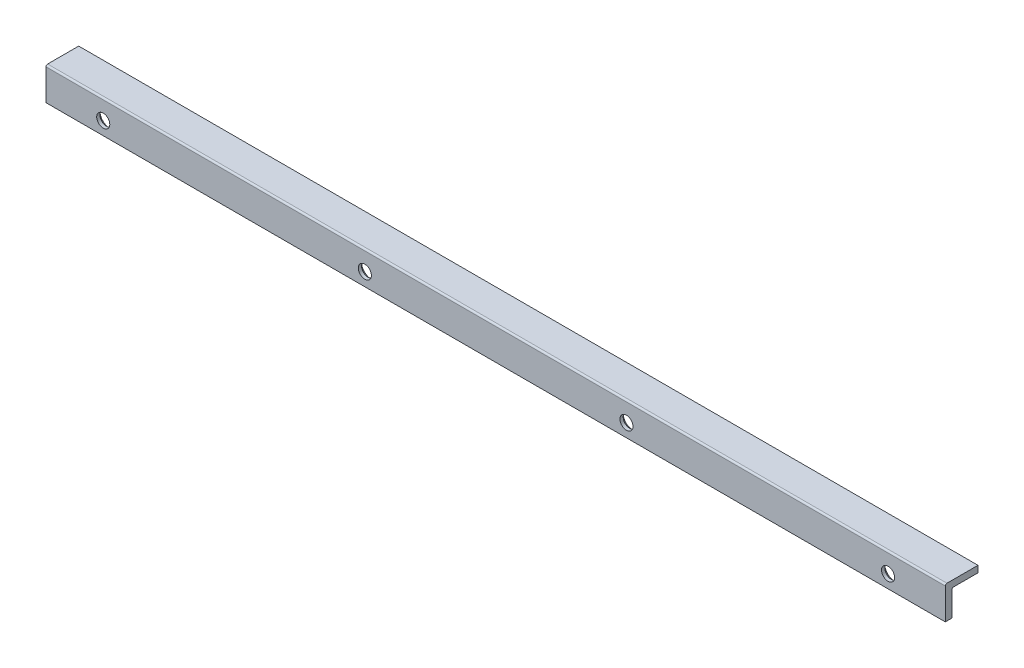
SolidWorks part; units mm, degrees
material "1060 Alloy"
ref_plane "Front Plane" through (0, 0, 0) normal (0, 0, 1) x (1, 0, 0)
ref_plane "Top Plane" through (0, 0, 0) normal (0, 1, 0) x (1, 0, 0)
ref_plane "Right Plane" through (0, 0, 0) normal (1, 0, 0) x (0, 0, -1)
sketch "Sketch1" plane through (0, 0, 0) normal (1, 0, 0) x (0, 0, -1)
  line L0 (0, -10) -> (0, -0.5)
  line L1 (0.5, 0) -> (10, 0)
  line L2 (10, 0) -> (10, -2)
  line L3 (10, -2) -> (2.5, -2)
  line L4 (0, -10) -> (2, -10)
  line L5 (2, -10) -> (2, -2.5)
  arc A0 (0, -0.5) -> (0.5, 0) centre (0.5, -0.5) cw
  arc A1 (2.5, -2) -> (2, -2.5) centre (2.5, -2.5) ccw
  point P10 (0, 0)
  dimension "D3" = 0.5
  dimension "D1" = 10
  dimension "D2" = 2
extrude "Boss-Extrude1" add sketch "Sketch1" along normal blind 137.5 and the other way blind 137.5
sketch "Sketch2" plane through (0, 0, 0) normal (0, 0, 1) x (1, 0, 0)
  line L0 (-40, 0) -> (40, 0) construction
  line L1 (-40, 0) -> (-120, 0) construction
  line L2 (40, 0) -> (120, 0) construction
  line L3 (-120, 0) -> (-120, -6) construction
  line L4 (-40, 0) -> (-40, -6) construction
  line L5 (40, 0) -> (40, -6) construction
  line L6 (120, 0) -> (120, -6) construction
  circle A0 centre (-120, -6) radius 2
  circle A1 centre (-40, -6) radius 2
  circle A2 centre (40, -6) radius 2
  circle A3 centre (120, -6) radius 2
  point P4 (0, 0)
  dimension "D4" = 4
  dimension "D1" = 80
  dimension "D2" = 240
  dimension "D3" = 6
extrude "Cut-Extrude1" cut sketch "Sketch2" against normal through all
chamfer "Chamfer1" distance 1 angle 45 4 edges at (-122, -6, -2) (-42, -6, -2) (38, -6, -2) (118, -6, -2)
